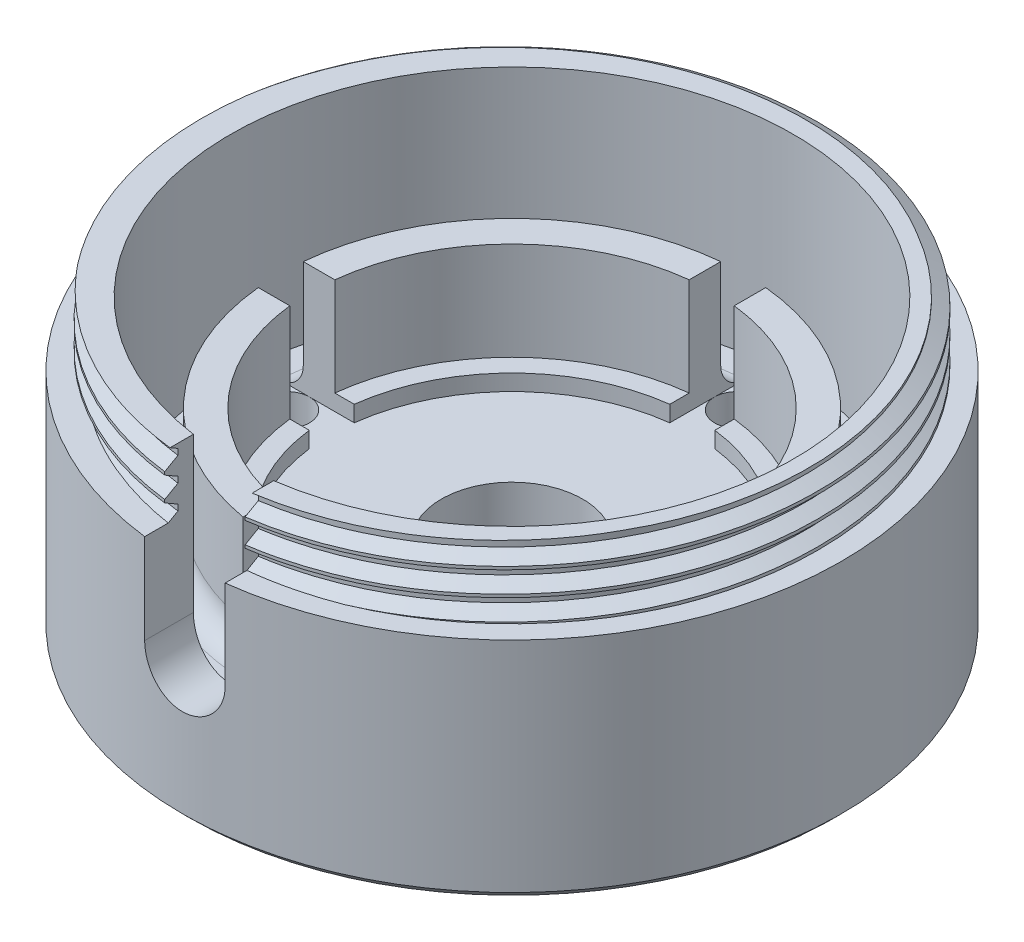
SolidWorks part; units mm, degrees
ref_plane "Front plane" through (0, 0, 0) normal (0, 0, 1) x (1, 0, 0)
ref_plane "Top plane" through (0, 0, 0) normal (0, 1, 0) x (1, 0, 0)
ref_plane "Right plane" through (0, 0, 0) normal (1, 0, 0) x (0, 0, -1)
ref_axis "Axis X" through (0, 0, 0) along (1, 0, 0)
ref_axis "Axis Y" through (0, 0, 0) along (0, 1, 0)
ref_axis "Axis Z" through (0, 0, 0) along (0, 0, 1)
sketch "Sketch1" plane through (0, 0, 0) normal (0, 1, 0) x (1, 0, 0)
  circle A0 centre (0, 0) radius 20.5
  circle A1 centre (0, 0) radius 4.4
  circle A2 centre (0, 0) radius 14 construction
  circle A3 centre (0, 14) radius 1.4
  circle A4 centre (14, 0) radius 1.4
  circle A5 centre (0, -14) radius 1.4
  circle A6 centre (-14, 0) radius 1.4
  point P16 (0, 0)
  dimension "D1" = 41
  dimension "D2" = 8.8
  dimension "D3" = 28
  dimension "D4" = 2.8
  dimension "D5" = 4
extrude "Extrude1" add sketch "Sketch1" along normal blind 5
sketch "Sketch2" plane through (0, 5, 0) normal (0, 1, 0) x (1, 0, 0)
  line L0 (-1.4, 14.382) -> (-1.4, 11.2129)
  line L2 (1.4, 14.382) -> (1.4, 11.2129)
  line L4 (14.382, -1.4) -> (11.2129, -1.4)
  line L5 (14.382, 1.4) -> (11.2129, 1.4)
  line L6 (-1.4, -14.382) -> (-1.4, -11.2129)
  line L7 (1.4, -14.382) -> (1.4, -11.2129)
  line L8 (-14.382, 1.4) -> (-11.2129, 1.4)
  line L9 (-14.382, -1.4) -> (-11.2129, -1.4)
  arc A8 (-1.4, 11.2129) -> (-11.2129, 1.4) centre (0, 0) ccw
  arc A9 (-1.4, 14.382) -> (-14.382, 1.4) centre (0, 0) ccw
  circle A10 centre (0, 14) radius 1.4 construction
  circle A11 centre (14, 0) radius 1.4 construction
  arc A12 (11.2129, 1.4) -> (1.4, 11.2129) centre (0, 0) ccw
  arc A13 (14.382, 1.4) -> (1.4, 14.382) centre (0, 0) ccw
  arc A14 (1.4, -11.2129) -> (11.2129, -1.4) centre (0, 0) ccw
  arc A15 (1.4, -14.382) -> (14.382, -1.4) centre (0, 0) ccw
  arc A16 (-14.382, -1.4) -> (-1.4, -14.382) centre (0, 0) ccw
  arc A17 (-11.2129, -1.4) -> (-1.4, -11.2129) centre (0, 0) ccw
  point P24 (0, 0)
  dimension "D1" = 22.6
  dimension "D2" = 28.9
  dimension "D3" = 4
extrude "Extrude2" add sketch "Sketch2" along normal blind 7.1
sketch "Sketch7" plane through (0, 12.1, 0) normal (0, 1, 0) x (1, 0, 0)
  circle A0 centre (0, 0) radius 12.5
  dimension "D1" = 25
extrude "Extrude5" cut sketch "Sketch7" against normal offset from surface (6.1 mm away) 1 up to face at (0, 5, 4.4)
fillet "Fillet1" radius 1.5 4 edges at (-10.2177, 5, -10.2177) (10.2177, 5, -10.2177) (10.2177, 5, 10.2177) (-10.2177, 5, 10.2177)
sketch "Sketch8" plane through (0, 5, 0) normal (0, 1, 0) x (1, 0, 0)
  circle A0 centre (0, 0) radius 20.5
  circle A1 centre (0, 0) radius 17.5
  circle A2 centre (0, 0) radius 20.5 construction
  dimension "D1" = 35
extrude "Extrude6" add sketch "Sketch8" along normal blind 9.1
sketch "Sketch4" plane through (0, 14.1, 0) normal (0, 1, 0) x (1, 0, 0)
  circle A0 centre (0, 0) radius 17.5
  circle A1 centre (0, 0) radius 18.45
  dimension "D1" = 35
  dimension "D2" = 0.95
extrude "Extrude4" add sketch "Sketch4" along normal blind 4
thread "Thread1" pitch 1.5 method extrude trim with start face yes trim with end face yes profile "Sketch6" start angle 0, offset 2, length 0, pitch 1.5, diameter 36.9
ref_plane "Plane1" through (-18.45, 20.1, 0) normal (0, 0, 1) x (-1, 0, 0)
sketch "Sketch6" plane through (-18.45, 20.1, 0) normal (0, 0, 1) x (-1, 0, 0)
  line L0 (0, 0) -> (0, 1.5) construction
  line L1 (0, 0) -> (0.8119, 0.4687)
  line L2 (0.8119, 0.4687) -> (0.8119, 0.6562)
  line L3 (0.8119, 0.6562) -> (0, 1.125)
  line L4 (0.8119, 0.5625) -> (0, 0.5625) construction
  line L11 (0, 0) -> (0, 1.125)
  point P2 (0, 0)
  dimension "Pitch" = 1.5
  dimension "Profile_Angle" = 60
  dimension "Profile_Land" = 0.1875
  dimension "Profile_Height" = 0.8119
chamfer "Chamfer2" distance 1.5 angle 45 1 edges at (0, 0, 4.4)
chamfer "Chamfer3" distance 0.5 angle 45 1 edges at (0, 0, 20.5)
chamfer "Chamfer4" distance 1 angle 45 4 edges at (0, 0, -12.6) (14, 0, 1.4) (-14, 0, 1.4) (0, 0, 15.4)
sketch "Sketch9" plane through (0, 0, 0) normal (0, 0, 1) x (1, 0, 0)
  line L0 (-1.4, 6) -> (-11.2129, 6) construction
  line L1 (-2.5, 8.5) -> (-2.5, 19.1)
  line L2 (-2.5, 19.1) -> (2.5, 19.1)
  line L3 (2.5, 19.1) -> (2.5, 8.5)
  line L4 (17.5, 18.1) -> (-17.5, 18.1) construction
  arc A0 (-2.5, 8.5) -> (2.5, 8.5) centre (0, 8.5) ccw
  dimension "D2" = 5
  dimension "D1" = 2.5
  dimension "D3" = 1
extrude "Extrude7" cut sketch "Sketch9" along normal through all
equation "\"motor_D\"= 30'Motor diameter"
equation "\"motor_H\"= 13'Motor heigh"
equation "\"motor_d1\"= 25.4558'Seating diameter of screws on the fixed part of the motor"
equation "\"motor_s1\"= 2'Screws diameter on the fixed part of motor"
equation "\"motor_a2\"= 10'Seating parameter in rectangle of screws on the moving part of the motor"
equation "\"motor_s2\"= 2'Screws diameter on the moving part of motor"
equation "\"motor_Dc\"= 5'Central hole diameter of motor"
equation "\"bearing_d1\"= 8'Bearing inner diameter"
equation "\"bearing_d2\"= 16'Bearing external diameter"
equation "\"bearing h\"= 5'Bearing heigh"
equation "\"pin_d\"= 2'Pin diameter"
equation "\"pin_h\"= 12'Pin heigh"
equation "\"magnet_d1\"= 5'Magnet inner diameter"
equation "\"magnet_d2\"= 9.5'Magnet external diameter"
equation "\"magnet_h\"= 3'Magnet heigh"
equation "\"motor_b2\"= 22'Seating parameter in rectangle of screws on the moving part of the motor"
equation "\"motor_d2\"= 0'Seating diameter of screws on the moving part of the motor (if this parameter is not determine, write 0)"
equation "\"motor_cmd\"= 12'Central magnet mount diameter"
equation "\"motor_cmh\"= 1.4'Central magnet mount heigh (if not write 0)"
equation "\"motor_whR\"= 10'Distance from center of motor to wires"
equation "\"D1@Sketch1\" = IIF ( \"motor_D\" < 34 , 41 , \"motor_D\" + 8 )"
equation "\"D2@Sketch1\"=\"ft_sensor_d1\"-1"
equation "\"D4@Sketch1\"=3-\"print_offset\""
equation "\"D1@Extrude2\"=\"ft_sensor_h\""
equation "\"D1@Sketch4\" = IIF ( \"motor_D\" < 34 , 41 , \"motor_D\" + 8 ) - 6"
equation "\"print_offset\"= 0.2'Offset for printing holes"
equation "\"D2@Sketch4\"=0.95"
equation "\"ft_sensor_d1\"= 9.8"
equation "\"ft_sensor_d2\"= 24.9"
equation "\"ft_sensor_d3\"= 22.6'Inner diameter of "
equation "\"ft_sensor_h\"= 7.1"
equation "\"ft_sensor_whD\" = 5"
equation "\"D1@Sketch2\"=\"ft_sensor_d3\""
equation "\"D2@Sketch2\"=\"ft_sensor_d2\"+4"
equation "\"D1@Sketch7\"=\"ft_sensor_d2\"+\"print_offset\"/2"
equation "\"D1@Sketch8\" = IIF ( \"motor_D\" < 34 , 41 , \"motor_D\" + 8 ) - 6"
equation "\"D1@Extrude6\"=\"ft_sensor_h\"+1+1"
equation "\"D1@Sketch9\"=\"ft_sensor_whD\"/2"
equation "\"D2@Sketch9\"=\"ft_sensor_whD\""
